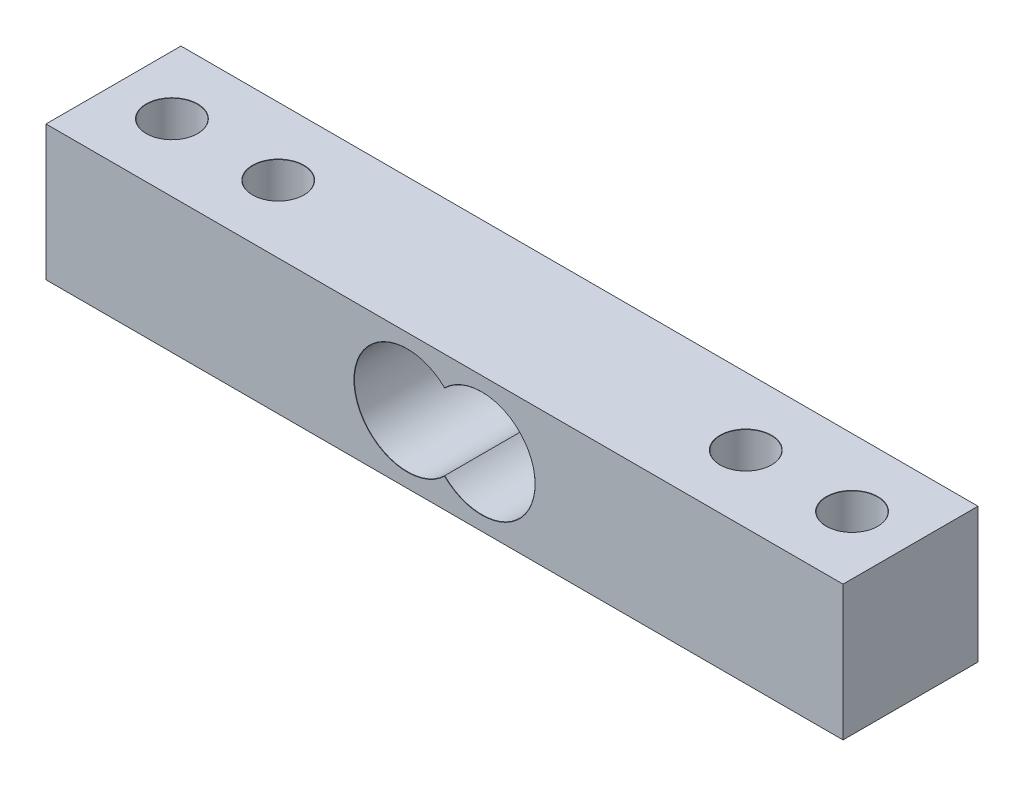
SolidWorks part; units mm, degrees
ref_plane "Front Plane" through (0, 0, 0) normal (0, 0, 1) x (1, 0, 0)
ref_plane "Top Plane" through (0, 0, 0) normal (0, 1, 0) x (1, 0, 0)
ref_plane "Right Plane" through (0, 0, 0) normal (1, 0, 0) x (0, 0, -1)
sketch "Sketch1" plane through (0, 0, 0) normal (0, 1, 0) x (1, 0, 0)
  line L1 (-37.5, -6.35) -> (37.5, -6.35)
  line L2 (-37.5, -6.35) -> (-37.5, 6.35)
  line L3 (-37.5, 6.35) -> (37.5, 6.35)
  line L4 (37.5, -6.35) -> (37.5, 6.35)
  line L5 (-37.5, -6.35) -> (37.5, 6.35) construction
  line L6 (-37.5, 6.35) -> (37.5, -6.35) construction
  point P0 (0, 0)
  dimension "D1" = 12.7
  dimension "D2" = 75
extrude "Boss-Extrude1" add sketch "Sketch1" along normal blind 12.7
hole_wizard "M4 Clearance Hole1" positions "Sketch2" profile "Sketch3" hole size "M4" standard "ANSI Metric" end condition through all
sketch "Sketch2" plane through (0, 12.7, 0) normal (0, 1, 0) x (1, 0, 0)
  line L0 (-32, 0) -> (-22, 0) construction
  line L1 (22, 0) -> (32, 0) construction
  line L3 (-22, 0) -> (22, 0) construction
  point P0 (-32, 0)
  point P2 (-22, 0)
  point P15 (0, 0)
  point P18 (22, 0)
  point P21 (32, 0)
  dimension "D1" = 10
  dimension "D2" = 44
sketch "Sketch3" plane through (-32, 12.7, 0) normal (1, 0, 0) x (0, 0, 1)
  line L0 (0, 0) -> (0, 12.7)
  line L1 (0, 12.7) -> (2.4, 12.7)
  line L2 (2.4, 12.7) -> (2.4, 0.021)
  line L3 (2.4, 0.021) -> (2.425, 0)
  line L5 (2.425, 0) -> (0, 0)
  line L6 (-2.4, 0.021) -> (-2.425, 0) construction
  line L11 (0, -6.35) -> (0, 107.95) construction
  dimension "Thru Hole Dia." = 4.8
  dimension "Thru Hole Depth" = 12.7
  dimension "Near C'Sink Dia." = 4.85
  dimension "Near C'Sink Angle" = 100
hole_wizard "M8 Clearance Hole1" positions "Sketch4" profile "Sketch5" hole size "M8" standard "ANSI Metric" end condition through all
sketch "Sketch4" plane through (0, 0, 6.35) normal (0, 0, 1) x (1, 0, 0)
  line L0 (-3.5, 6.35) -> (3.5, 6.35) construction
  line L2 (-37.5, 12.7) -> (-37.5, 0) construction
  point P0 (-3.5, 6.35)
  point P2 (3.5, 6.35)
  point P9 (0, 6.35)
  point P13 (-37.5, 6.35)
  dimension "D1" = 7
sketch "Sketch5" plane through (-3.5, 6.35, 6.35) normal (1, 0, 0) x (0, -1, 0)
  line L0 (0, 0) -> (0, 12.7)
  line L1 (0, 12.7) -> (5, 12.7)
  line L2 (5, 12.7) -> (5, 0.021)
  line L3 (5, 0.021) -> (5.025, 0)
  line L5 (5.025, 0) -> (0, 0)
  line L6 (-5, 0.021) -> (-5.025, 0) construction
  line L11 (0, -6.35) -> (0, 107.95) construction
  dimension "Thru Hole Dia." = 10
  dimension "Thru Hole Depth" = 12.7
  dimension "Near C'Sink Dia." = 10.05
  dimension "Near C'Sink Angle" = 100
